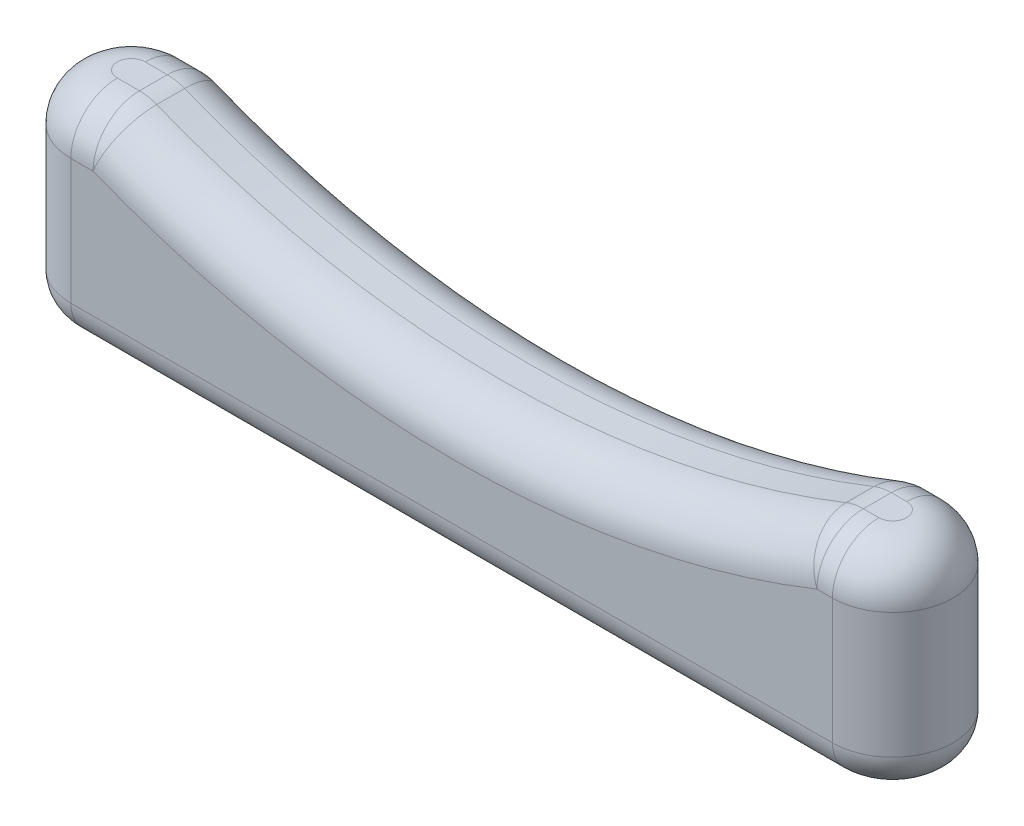
SolidWorks part; units mm, degrees
ref_plane "Front Plane" through (0, 0, 0) normal (0, 0, 1) x (1, 0, 0)
ref_plane "Top Plane" through (0, 0, 0) normal (0, 1, 0) x (1, 0, 0)
ref_plane "Right Plane" through (0, 0, 0) normal (1, 0, 0) x (0, 0, -1)
sketch "Sketch1" plane through (0, 0, 0) normal (0, 1, 0) x (1, 0, 0)
  line L0 (-82, 0) -> (82, 0) construction
  line L1 (-55, 0) -> (55, 0) construction
  line L2 (-82, 13) -> (82, 13)
  line L3 (-82, -13) -> (82, -13)
  line L4 (0, -55) -> (0, 55) construction
  arc A0 (-82, 13) -> (-82, -13) centre (-82, 0) ccw
  arc A1 (82, -13) -> (82, 13) centre (82, 0) ccw
  point P5 (0, 0)
  dimension "D1" = 13
  dimension "D2" = 164
  dimension "D3" = 82
extrude "Boss-Extrude1" add sketch "Sketch1" against normal blind 45
sketch "Sketch2" plane through (0, -45, 0) normal (0, -1, 0) x (1, 0, 0)
  line L0 (24.75, 0) -> (-24.75, 0) construction
  line L1 (0, -14.3) -> (0, 14.3) construction
  circle A0 centre (-54, 0) radius 11
  circle A1 centre (54, 0) radius 11
  point P8 (-182.0189, 50.8396)
  dimension "D2" = 11
  dimension "D3" = 108
  dimension "D4" = 54
extrude "Cut-Extrude1" cut sketch "Sketch2" against normal blind 15
sketch "Sketch4" plane through (0, 0, 0) normal (0, 0, 1) x (1, 0, 0)
  line L0 (-82, -45) -> (82, -45) construction
  circle A0 centre (0.7248, 185) radius 200
  dimension "D1" = 400
  dimension "D2" = 30
extrude "Cut-Extrude2" cut sketch "Sketch4" against normal mid plane 35
fillet "Fillet1" radius 8 4 edges at (0, -45, -13) (95, -45, 0) (0, -45, 13) (-95, -45, 0)
fillet "Fillet2" radius 10 8 edges at (-78.6343, 0, -13) (-78.6343, 0, 13) (79.3591, 0, 13) (79.3591, 0, -13) (-95, 0, 0) (95, 0, 0) (0.7248, -15, 13) (0.7248, -15, -13)
fillet "Fillet3" radius 10 6 edges at (77.1359, -2.1215, -9.1587) (76.7183, 0, 0) (-75.6862, -2.1215, -9.1587) (-75.2686, 0, 0) (77.1359, -2.1215, 9.1587) (-75.6862, -2.1215, 9.1587)
